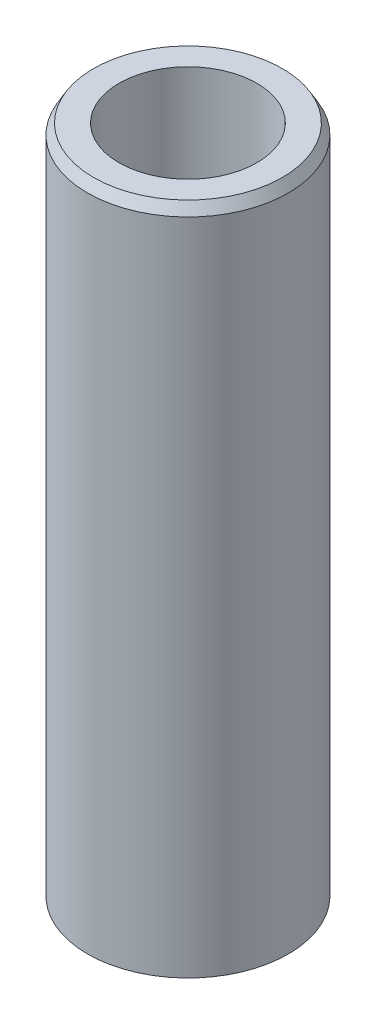
SolidWorks part; units mm, degrees
ref_plane "Front Plane" through (0, 0, 0) normal (0, 0, 1) x (1, 0, 0)
ref_plane "Top Plane" through (0, 0, 0) normal (0, 1, 0) x (1, 0, 0)
ref_plane "Right Plane" through (0, 0, 0) normal (1, 0, 0) x (0, 0, -1)
sketch "Sketch1" plane through (0, 0, 0) normal (0, 1, 0) x (1, 0, 0)
  circle A0 centre (0, 0) radius 55
  dimension "SHAFT_OD" = 110
extrude "Boss-Extrude1" add sketch "Sketch1" along normal blind 370.0177
sketch "Sketch2" plane through (0, 0, 0) normal (0, 1, 0) x (1, 0, 0)
  circle A0 centre (0, 0) radius 37.7479
  dimension "BORE_D" = 75.4957
extrude "Cut-Extrude1" cut sketch "Sketch2" along normal through all
chamfer "Chamfer1" distance 5.7081 angle 30 2 edges at (0, 370.0177, 55) (0, 0, 55) first distance on face at (0, 370.0177, 55) first distance on face at (0, 0, 37.7479)
